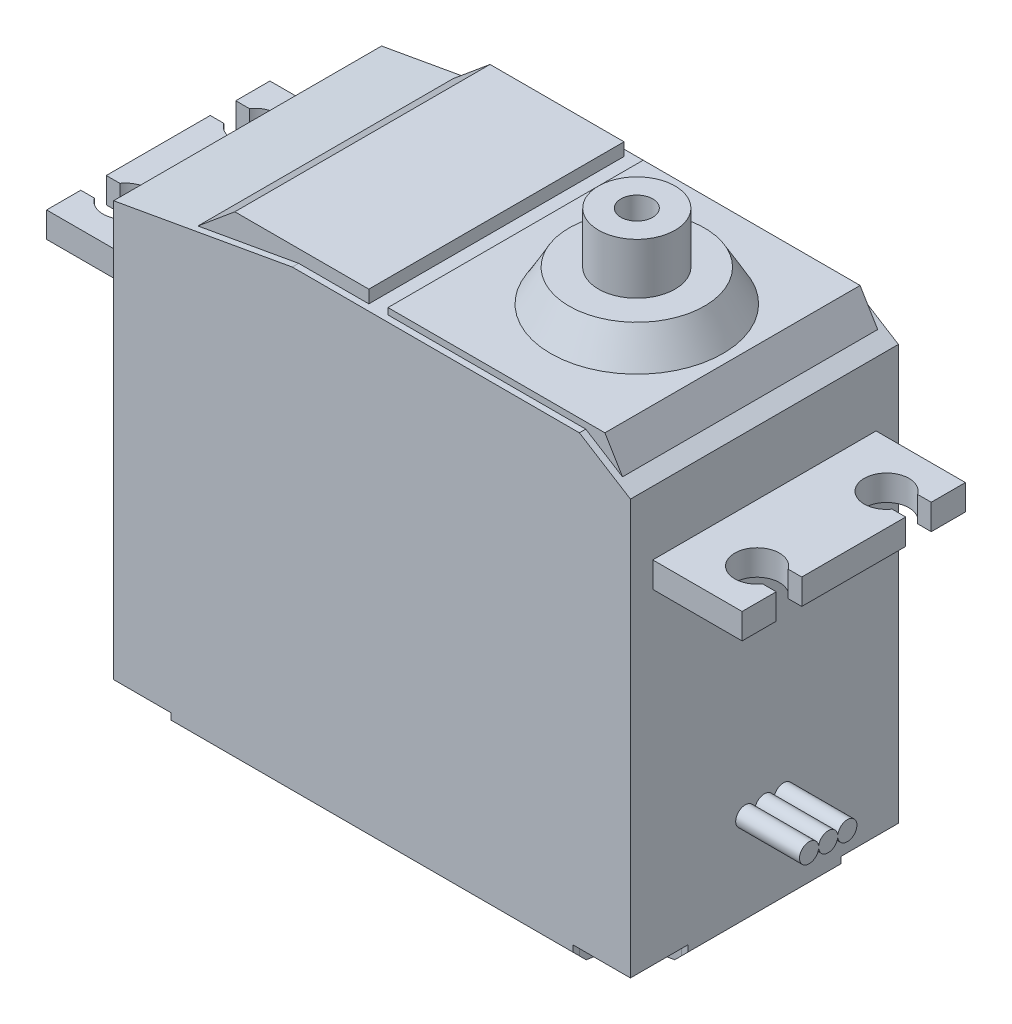
SolidWorks part; units mm, degrees
ref_plane "Front Plane" through (0, 0, 0) normal (0, 0, 1) x (1, 0, 0)
ref_plane "Top Plane" through (0, 0, 0) normal (0, 1, 0) x (1, 0, 0)
ref_plane "Right Plane" through (0, 0, 0) normal (1, 0, 0) x (0, 0, -1)
sketch "Sketch1" plane through (0, 0, 0) normal (0, 1, 0) x (1, 0, 0)
  line L1 (-29.5162, 11.3427) -> (11.6318, 11.3427)
  line L2 (-29.5162, 11.3427) -> (-29.5162, -9.9933)
  line L3 (-29.5162, -9.9933) -> (11.6318, -9.9933)
  line L4 (11.6318, 11.3427) -> (11.6318, -9.9933)
  dimension "D1" = 21.336
  dimension "D2" = 41.148
extrude "Boss-Extrude1" add sketch "Sketch1" along normal blind 37.084
chamfer "Chamfer1" distance 2.54 distance2 14.224 1 edges at (-29.5162, 37.084, -0.6747) first distance on face at (-29.5162, 18.542, -0.6747)
chamfer "Chamfer2" distance 2.54 distance2 4.064 1 edges at (11.6318, 37.084, -0.6747) first distance on face at (11.6318, 18.542, -0.6747)
ref_plane "Plane1" through (0, 35.052, 0) normal (0, 1, 0) x (1, 0, 0)
sketch "Sketch3" plane through (0, 35.052, 0) normal (0, 1, 0) x (1, 0, 0)
  line L1 (-8.1802, 10.8347) -> (10.6158, 10.8347)
  line L2 (-8.1802, 10.8347) -> (-8.1802, -9.4853)
  line L3 (-8.1802, -9.4853) -> (10.6158, -9.4853)
  line L4 (10.6158, 10.8347) -> (10.6158, -9.4853)
  line L6 (11.6318, 11.3427) -> (11.6318, -9.9933) construction
  line L8 (7.5678, 11.3427) -> (-15.2922, 11.3427) construction
  line L9 (-15.2922, -9.9933) -> (7.5678, -9.9933) construction
  dimension "D1" = 1.016
  dimension "D2" = 18.796
  dimension "D3" = 0.508
  dimension "D4" = 0.508
extrude "Boss-Extrude2" add sketch "Sketch3" along normal blind 2.54
chamfer "Chamfer3" distance 2.54 distance2 1.524 1 edges at (10.6158, 37.592, -0.6747) first distance on face at (10.6158, 36.3855, -0.6747)
ref_plane "Plane2" through (0, 34.544, 0) normal (0, 1, 0) x (1, 0, 0)
sketch "Sketch4" plane through (0, 34.544, 0) normal (0, 1, 0) x (1, 0, 0)
  line L0 (-15.2922, -9.9933) -> (-29.5162, -9.9933) construction
  line L1 (-23.4202, 10.8347) -> (-9.7042, 10.8347)
  line L2 (-23.4202, 10.8347) -> (-23.4202, -9.4853)
  line L3 (-23.4202, -9.4853) -> (-9.7042, -9.4853)
  line L4 (-9.7042, 10.8347) -> (-9.7042, -9.4853)
  line L5 (-29.5162, 11.3427) -> (-15.2922, 11.3427) construction
  line L6 (-29.5162, -9.9933) -> (-29.5162, 11.3427) construction
  dimension "D1" = 0.508
  dimension "D2" = 0.508
  dimension "D3" = 19.812
  dimension "D4" = 6.096
extrude "Boss-Extrude3" add sketch "Sketch4" along normal blind 3.556
chamfer "Chamfer4" distance 2.54 distance2 3.048 1 edges at (-23.4202, 38.1, -0.6747) first distance on face at (-23.4202, 36.8663, -0.6747)
sketch "Sketch5" plane through (0, 37.592, 0) normal (0, 1, 0) x (1, 0, 0)
  line L0 (-8.1802, 0.6747) -> (1.4718, 0.6747) construction
  line L1 (-8.1802, -9.4853) -> (-8.1802, 10.8347) construction
  line L2 (-8.1802, 10.8347) -> (-8.1802, -9.4853) construction
  circle A0 centre (1.4718, 0.6747) radius 6.858
  dimension "D2" = 13.716
  dimension "D1" = 9.652
extrude "Boss-Extrude4" add sketch "Sketch5" along normal blind 2.54 draft 30
sketch "Sketch6" plane through (0, 40.132, 0) normal (0, 1, 0) x (1, 0, 0)
  circle A0 centre (1.4718, 0.6747) radius 5.3915 construction
  circle A1 centre (1.4718, 0.6747) radius 5.3915 construction
  circle A2 centre (1.4718, 0.6747) radius 3.048
  circle A3 centre (1.4718, 0.6747) radius 1.27
  dimension "D1" = 2.54
  dimension "D2" = 6.096
extrude "Boss-Extrude5" add sketch "Sketch6" along normal blind 4.064
ref_plane "Plane3" through (0, 27.432, 0) normal (0, -1, 0) x (-1, 0, 0)
sketch "Sketch7" plane through (0, 27.432, 0) normal (0, -1, 0) x (-1, 0, 0)
  line L1 (29.5162, 9.5647) -> (36.6282, 9.5647)
  line L2 (29.5162, 9.5647) -> (29.5162, -8.2153)
  line L3 (29.5162, -8.2153) -> (36.6282, -8.2153)
  line L4 (36.6282, 9.5647) -> (36.6282, 6.845)
  line L5 (29.5162, 0.6747) -> (36.6282, 0.6747) construction
  line L6 (29.5162, 11.3427) -> (29.5162, -9.9933) construction
  line L7 (35.5473, -3.4637) -> (36.6282, -3.4637)
  line L8 (35.5473, -5.4957) -> (36.6282, -5.4957)
  line L9 (36.6282, -5.4957) -> (36.6282, -8.2153)
  line L10 (35.5473, 6.845) -> (36.6282, 6.845)
  line L11 (35.5473, 4.813) -> (36.6282, 4.813)
  line L12 (36.6282, 4.813) -> (36.6282, -3.4637)
  arc A0 (35.5473, -3.4637) -> (35.5473, -5.4957) centre (34.0882, -4.4797) ccw
  arc A1 (35.5473, 4.813) -> (35.5473, 6.845) centre (34.0882, 5.829) cw
  point P6 (29.5162, 0.6747)
  dimension "D3" = 3.556
  dimension "D1" = 17.78
  dimension "D2" = 7.112
  dimension "D4" = 2.54
  dimension "D5" = 1.016
  dimension "D6" = 2.032
extrude "Boss-Extrude6" add sketch "Sketch7" against normal blind 2.032
ref_plane "Plane4" through (-8.9422, 0, 0) normal (1, 0, 0) x (0, 0, -1)
mirror "Mirror1" about plane through (-8.9422, 0, 0) normal (1, 0, 0) of "Boss-Extrude6"
chamfer "Chamfer5" distance 1.016 distance2 1.016 4 edges at (-29.5162, 0, -0.6747) (-8.9422, 0, -11.3427) (-8.9422, 0, 9.9933) (11.6318, 0, -0.6747)
sketch "Sketch8" plane through (0, 0, 0) normal (0, -1, 0) x (1, 0, 0)
  line L0 (-29.5162, 9.9933) -> (11.6318, 9.9933) construction
  line L1 (-29.5162, -11.3427) -> (-29.5162, 9.9933) construction
  line L2 (11.6318, -11.3427) -> (-29.5162, -11.3427) construction
  line L3 (11.6318, 9.9933) -> (11.6318, -11.3427) construction
  line L4 (-29.5162, 9.9933) -> (-24.9442, 9.9933)
  line L5 (-29.5162, -11.3427) -> (-29.5162, -6.7707)
  line L6 (11.6318, -11.3427) -> (7.0598, -11.3427)
  line L7 (11.6318, 9.9933) -> (11.6318, 5.4213)
  line L8 (-29.5162, -0.6747) -> (10.6158, -0.6747) construction
  line L9 (10.6158, -10.3267) -> (10.6158, 8.9773) construction
  line L10 (-8.9422, 9.9933) -> (-8.9422, -11.3427) construction
  line L11 (-29.5162, 5.4213) -> (-29.0082, 5.4213)
  line L12 (-24.9442, 9.4853) -> (-24.9442, 9.9933)
  line L13 (7.0598, 9.4853) -> (7.0598, 9.9933)
  line L14 (11.6318, 5.4213) -> (11.1238, 5.4213)
  line L15 (11.6318, -6.7707) -> (11.1238, -6.7707)
  line L16 (7.0598, -10.8347) -> (7.0598, -11.3427)
  line L17 (-24.9442, -10.8347) -> (-24.9442, -11.3427)
  line L18 (-29.5162, -6.7707) -> (-29.0082, -6.7707)
  line L19 (-29.5162, 5.4213) -> (-29.5162, 9.9933)
  line L20 (7.0598, 9.9933) -> (11.6318, 9.9933)
  line L21 (-24.9442, -11.3427) -> (-29.5162, -11.3427)
  line L22 (11.6318, -6.7707) -> (11.6318, -11.3427)
  arc A0 (-24.9442, -10.8347) -> (-29.0082, -6.7707) centre (-29.0082, -10.8347) ccw
  arc A1 (11.1238, -6.7707) -> (7.0598, -10.8347) centre (11.1238, -10.8347) ccw
  arc A2 (7.0598, 9.4853) -> (11.1238, 5.4213) centre (11.1238, 9.4853) ccw
  arc A3 (-29.0082, 5.4213) -> (-24.9442, 9.4853) centre (-29.0082, 9.4853) ccw
  point P24 (-24.9442, -6.7707)
  point P27 (7.0598, -6.7707)
  point P30 (7.0598, 5.4213)
  point P33 (-24.9442, 5.4213)
  dimension "D3" = 4.064
  dimension "D1" = 4.572
  dimension "D2" = 4.572
extrude "Cut-Extrude1" cut sketch "Sketch8" against normal blind 1.524
sketch "Sketch9" plane through (11.6318, 0, 0) normal (1, 0, 0) x (0, 0, -1)
  line L0 (0.6747, 1.016) -> (0.6747, 8.128) construction
  line L1 (-5.4213, 1.016) -> (6.7707, 1.016) construction
  line L2 (0.6747, 8.128) -> (-0.0873, 8.128) construction
  line L3 (-0.098, 8.255) -> (-0.0767, 8.255)
  line L4 (1.426, 8.255) -> (1.4473, 8.255)
  line L5 (-0.098, 8.001) -> (-0.0767, 8.001)
  line L6 (1.426, 8.001) -> (1.4473, 8.001)
  line L7 (-0.8493, 8.128) -> (-0.0873, 8.128) construction
  arc A0 (-0.0767, 8.001) -> (1.426, 8.001) centre (0.6747, 8.128) ccw
  arc A1 (-0.098, 8.255) -> (-0.098, 8.001) centre (-0.8493, 8.128) ccw
  arc A2 (1.4473, 8.001) -> (1.4473, 8.255) centre (2.1987, 8.128) ccw
  arc A3 (1.426, 8.255) -> (-0.0767, 8.255) centre (0.6747, 8.128) ccw
  point P13 (0, 0)
  dimension "D1" = 1.524
  dimension "D2" = 7.112
  dimension "D3" = 0.254
  dimension "D4" = 0.254
extrude "Boss-Extrude7" add sketch "Sketch9" along normal blind 5.08
